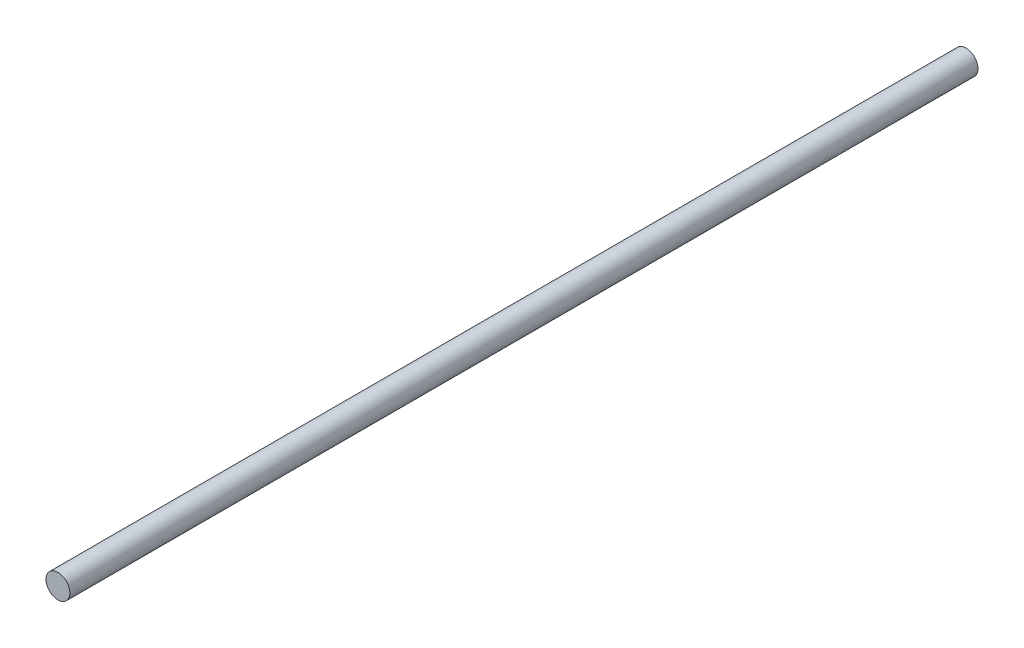
SolidWorks part; units mm, degrees
ref_plane "Front Plane" through (0, 0, 0) normal (0, 0, 1) x (1, 0, 0)
ref_plane "Top Plane" through (0, 0, 0) normal (0, 1, 0) x (1, 0, 0)
ref_plane "Right Plane" through (0, 0, 0) normal (1, 0, 0) x (0, 0, -1)
sketch "base" plane through (0, 0, 0) normal (0, 0, 1) x (1, 0, 0)
  circle A0 centre (0, 0) radius 50
  arc A4 (10, 48.9898) -> (-10, 48.9898) centre (0, 0) ccw construction
extrude "Boss-Extrude1" add sketch "base" along normal blind 2800 and the other way blind 1000
sketch "center" plane through (0, 0, 0) normal (0, 1, 0) x (1, 0, 0)
  line L0 (0, -2800) -> (0, 1000) construction
  line L1 (-50, -2800) -> (50, -2800) construction
  line L2 (50, 1000) -> (-50, 1000) construction
sketch "cutout" plane through (0, 0, 0) normal (0, 0, 1) x (1, 0, 0)
  circle A0 centre (0, 0) radius 48.5
  circle A1 centre (0, 0) radius 50 construction
  dimension "D1" = 1.5
extrude "Cut-Extrude1" cut sketch "cutout" against normal offset from surface 10 and the other way offset from surface 10 up to face at (50, 0, -1000) other way up to face at (50, 0, 2800)
